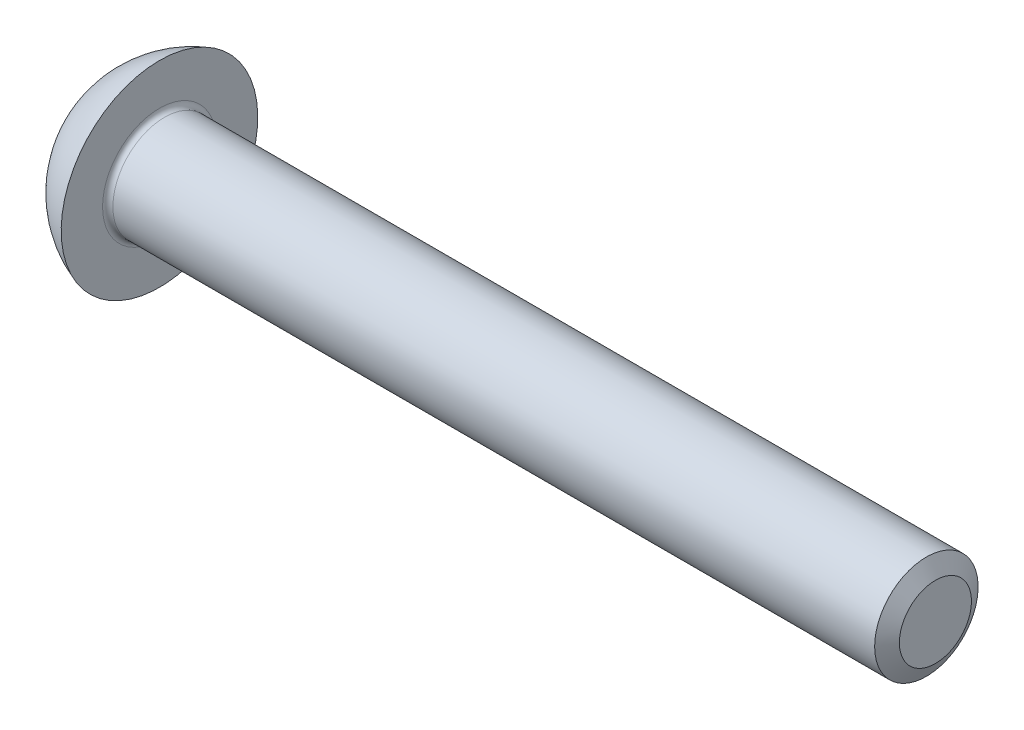
SolidWorks part; units mm, degrees
ref_plane "前视基准面" through (0, 0, 0) normal (0, 0, 1) x (1, 0, 0)
ref_plane "上视基准面" through (0, 0, 0) normal (0, 1, 0) x (1, 0, 0)
ref_plane "右视基准面" through (0, 0, 0) normal (1, 0, 0) x (0, 0, -1)
sketch "尺寸草图" plane through (0, 0, 0) normal (0, 0, 1) x (1, 0, 0)
  line L0 (0, 0) -> (30, 0) construction
  line L1 (30, 0) -> (30, 2) construction
  line L2 (30, 2) -> (29.3, 2) construction
  line L3 (0, 0) -> (0, 3.8) construction
  point P3 (1.4, 0)
  point P6 (30, 2.35)
  point P7 (0, 0.93)
  point P9 (2.2, 0)
  point P10 (2.4, 0)
  point P11 (30, 1.25)
  point P12 (3.7, 0)
  point P13 (4, 0)
  point P14 (30, 22.35)
  dimension "l" = 30
  dimension "d" = 4
  dimension "P" = 0.7
  dimension "a" = 1.4
  dimension "da" = 4.7
  dimension "dk" = 7.6
  dimension "e" = 2.87
  dimension "K" = 2.2
  dimension "r" = 0.2
  dimension "s" = 2.5
  dimension "t" = 1.3
  dimension "w" = 0.3
  dimension "zslwx" = 20
sketch "草图1" plane through (0, 0, 0) normal (0, 0, 1) x (1, 0, 0)
  line L0 (-32.2, 0) -> (0, 0) construction
  line L1 (0, 2) -> (-29.8, 2)
  line L2 (-30, 2.2) -> (-30, 3.8)
  line L3 (-32.2, 0) -> (-32.2, 2)
  line L4 (0, 2) -> (0, 0)
  line L5 (-32.2, 0) -> (0, 0)
  arc A0 (-30, 3.8) -> (-32.2, 2) centre (-28.7273, 0) ccw
  arc A1 (-29.8, 2) -> (-30, 2.2) centre (-29.8, 2.2) cw
  point P10 (-30, 2)
  dimension "r" = 0.2
  dimension "d" = 4
  dimension "dk" = 7.6
  dimension "k" = 2.2
  dimension "l" = 30
revolve "旋转1" add sketch "草图1" angle 360 about L0
cosmetic thread "装饰螺纹线1" parameters "D1"=20, "D2"=3.44
sketch "草图2" plane through (-32.2, 0, 0) normal (-1, 0, 0) x (0, 0, 1)
  line L1 (0, 1.4434) -> (-1.25, 0.7217)
  line L2 (-1.25, 0.7217) -> (-1.25, -0.7217)
  line L3 (-1.25, -0.7217) -> (0, -1.4434)
  line L4 (0, -1.4434) -> (1.25, -0.7217)
  line L5 (1.25, -0.7217) -> (1.25, 0.7217)
  line L6 (1.25, 0.7217) -> (0, 1.4434)
  circle A0 centre (0, 0) radius 1.25 construction
  dimension "s" = 2.5
extrude "切除-拉伸1" cut sketch "草图2" against normal blind 2.2
sketch "草图6" plane through (0, 0, 0) normal (0, 0, 1) x (1, 0, 0)
  line L0 (-30.9, 1.4434) -> (-30, 0)
  line L1 (-29.63, 1.4434) -> (-29.63, 0)
  line L2 (-29.63, 1.4434) -> (-30.9, 1.4434)
  line L3 (-32.2, 0) -> (-30, 0) construction
  line L4 (-29.63, 0) -> (-30, 0)
  line L5 (-32.2, 0) -> (-35.07, 0) construction
  dimension "t" = 1.3
  dimension "e-s" = 0.37
  dimension "k" = 2.2
  dimension "e" = 2.87
revolve "旋转2" add sketch "草图6" angle 360 about L3
sketch "草图7" plane through (0, 0, 0) normal (0, 0, 1) x (1, 0, 0)
  line L3 (-32.2, 1.4434) -> (-31.83, 0)
  line L4 (-32.2, 0) -> (-31.83, 0) construction
  line L7 (-32.2, 1.4434) -> (-32.2, 0)
  line L8 (-32.2, 0) -> (-31.83, 0)
  dimension "e-s" = 0.37
revolve "切除-旋转5" cut sketch "草图7" angle 360 about L4
sketch "草图4" plane through (0, 0, 0) normal (0, 0, 1) x (1, 0, 0)
  line L0 (-0.35, 2) -> (0, 1.3938)
  line L1 (-0.35, 2) -> (0.35, 2)
  line L2 (0.35, 2) -> (0, 1.3938)
  line L4 (0, -2) -> (0, 2) construction
  line L5 (-0.35, 0) -> (0.35, 0) construction
  dimension "d" = 2
  dimension "p" = 0.7
revolve "切除-旋转1" cut sketch "草图4" angle 360 about L5
ref_axis "基准轴1" through (-8.1887, 0, 0) along (1, 0, 0)
pattern_linear "阵列(线性)1" [suppressed] count 41 spacing 0.7 along (-1, 0, 0) of bodies 104
